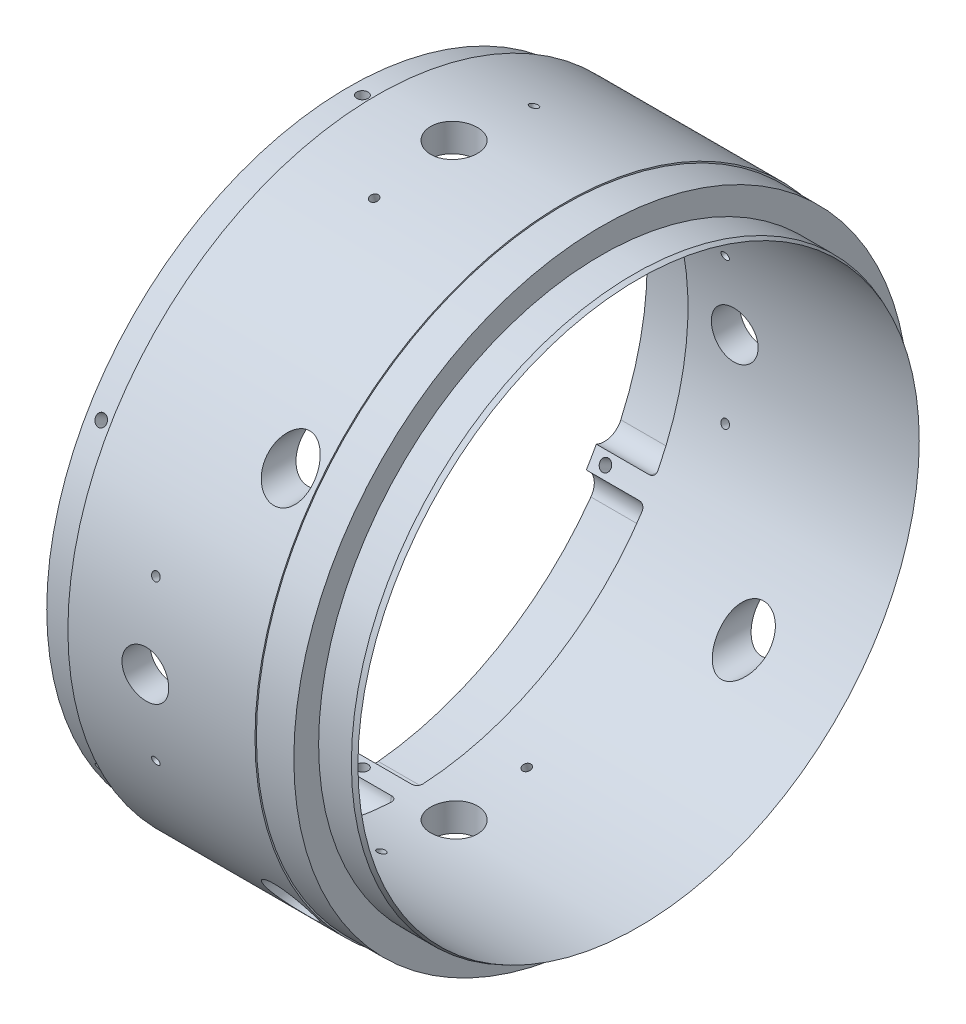
SolidWorks part; units mm, degrees
note: '?' marks a value the reader was unsure of.
material "6061-T6 (SS)"
ref_plane "Front" through (0, 0, 0) normal (0, 0, 1) x (1, 0, 0)
ref_plane "Top" through (0, 0, 0) normal (0, 1, 0) x (1, 0, 0)
ref_plane "Right" through (0, 0, 0) normal (1, 0, 0) x (0, 0, -1)
sketch "Sketch1" plane through (0, 0, 0) normal (0, 0, 1) x (1, 0, 0)
  line L0 (-10.16, 0.508) -> (-1.27, 0.508)
  line L1 (-71.12, 7.62) -> (-20.32, 7.62)
  line L2 (-10.16, 7.239) -> (-10.16, 0.508)
  line L3 (0, 0) -> (-78.7908, 0)
  line L4 (-1.27, 0.508) -> (0, 0)
  line L5 (-78.7908, 5.6896) -> (-78.7908, 0)
  line L6 (-71.12, 7.62) -> (-71.12, 5.6896)
  line L7 (-71.12, 5.6896) -> (-78.7908, 5.6896)
  line L8 (-44.3099, -76.2) -> (29.4033, -76.2) construction
  line L9 (-20.32, 7.62) -> (-20.32, 7.239)
  line L10 (-20.32, 7.239) -> (-10.16, 7.239)
  dimension "D1" = 7.6708
  dimension "D2" = 0.508
  dimension "D3" = 50.8
  dimension "D4" = 10.16
  dimension "D5" = 76.2
  dimension "D6" = 5.6896
  dimension "D7" = 6.731
  dimension "D8" = 0.381
  dimension "D9" = 10.16
  dimension "D10" = 1.27
revolve "Revolve2" add sketch "Sketch1" angle 360 about L8
ref_point "Point1"
ref_plane "Plane1" through (0, -76.2, 0) normal (0, 1, 0) x (1, 0, 0)
ref_plane "Plane2" through (0, -158.0896, 0) normal (0, -1, 0) x (-1, 0, 0)
hole_wizard "#31 (0.12) Diameter Hole1" positions "3DSketch1" profile "Sketch11" hole size "#31" standard "ANSI Inch"
sketch3d "3DSketch1"
  point P0 (-74.9808, -158.0896, 0)
  dimension "D1" = 3.81
sketch "Sketch11" plane through (-74.9808, -158.0896, 0) normal (1, 0, 0) x (0, 0, -1)
  line L0 (0, 0) -> (0, 185.9821)
  line L1 (0, 185.9821) -> (1.524, 185.9821)
  line L2 (1.524, 185.9821) -> (1.524, 0)
  line L5 (1.524, 0) -> (0, 0)
  line L11 (0, -6.35) -> (0, 107.95) construction
  dimension "Thru Hole Dia." = 3.048
  dimension "Thru Hole Depth" = 185.9821
pattern_circular "CirPattern4" count 6 over 360 about axis through (-44.3099, -76.2, 0) along (-1, 0, 0) of "#31 (0.12) Diameter Hole1"
sketch "Sketch8" plane through (-78.7908, 0, 0) normal (-1, 0, 0) x (0, 0, 1)
  line L0 (-7.6343, -152.0166) -> (0, -76.2) construction
  line L1 (0, -76.2) -> (0, -152.4) construction
  line L2 (-61.8419, -120.7198) -> (0, -76.2) construction
  line L3 (0, -76.2) -> (-65.9911, -114.3) construction
  circle A0 centre (0, -76.2) radius 76.2 construction
  arc A1 (-65.841, -123.5988) -> (-8.128, -156.9194) centre (0, -76.2) ccw
  circle A2 centre (0, -76.2) radius 81.8896 construction
  circle A3 centre (0, -76.2) radius 76.2
  arc A4 (-64.5901, -116.6297) -> (-2.7181, -152.3515) centre (0, -76.2) ccw
  circle A5 centre (0, -76.2) radius 81.8896
  circle A6 centre (-61.8419, -120.7198) radius 4.9276
  circle A7 centre (-7.6343, -152.0166) radius 4.9276
  arc A8 (-1.524, -158.0754) -> (1.524, -158.0754) centre (0, -76.2) ccw construction
  arc A9 (-1.524, -152.3848) -> (1.524, -152.3848) centre (0, -76.2) ccw construction
  arc A10 (-1.524, -158.0754) -> (1.524, -158.0754) centre (0, -76.2) ccw
  arc A11 (-1.524, -152.3848) -> (1.524, -152.3848) centre (0, -76.2) ccw
  arc A12 (-64.5901, -116.6297) -> (-2.7181, -152.3515) centre (0, -76.2) ccw
  arc A13 (-66.7399, -112.9726) -> (-65.2159, -115.6122) centre (0, -76.2) ccw construction
  arc A14 (-66.7399, -112.9726) -> (-65.2159, -115.6122) centre (0, -76.2) ccw
  arc A15 (-71.6682, -115.8179) -> (-70.1442, -118.4575) centre (0, -76.2) ccw construction
  arc A16 (-71.6682, -115.8179) -> (-70.1442, -118.4575) centre (0, -76.2) ccw
  point P3 (0, -152.4)
  point P14 (-8.128, -156.9194)
  point P16 (-65.841, -123.5988)
  point P20 (-65.9911, -114.3)
  dimension "D2" = 5.75
  dimension "D3" = 0.762
  dimension "D4" = 5.75
  dimension "D1" = 0
extrude "Cut-Extrude1" cut sketch "Sketch8" against normal blind 16.002
fillet "Fillet1" radius 1.5875 3 edges at (-62.7888, -155.7816, -4.4553) (-62.7888, -146.4586, -40.5638) (-62.7888, -119.8492, -66.692)
pattern_circular "CirPattern3" count 6 over 360 about axis through (0, -76.2, 0) along (1, 0, 0) of "Cut-Extrude1", "Fillet1"
sketch3d "3DSketch2"
  circle A0 centre (-24.9799, -157.9493, -0.0042) radius 2.0193
  point P2 (-24.9799, -155.93, -0.0042)
  dimension "D1" = 4.0386
sketch "Sketch12" plane through (0, 0, 0) normal (0, 0, 1) x (1, 0, 0)
  line L0 (-71.12, -76.2) -> (-20.32, -76.2) construction
  line L1 (-62.7888, -41.8886) -> (-62.7888, -110.5114) construction
  line L3 (-71.12, 7.62) -> (-71.12, -160.02) construction
  line L4 (-20.32, -159.639) -> (-20.32, 7.239) construction
  line L5 (-50.0888, -76.2) -> (-50.0888, 7.62) construction
  line L7 (-20.32, 7.62) -> (-71.12, 7.62) construction
  circle A0 centre (-50.0888, -76.2) radius 6.35
  dimension "D1" = 12.7
  dimension "D2" = 12.7
extrude "Cut-Extrude2" cut sketch "Sketch12" against normal through all
mirror "Mirror1" about plane through (0, 0, 0) normal (0, 0, 1) of "Cut-Extrude2"
sketch "Sketch13" plane through (0, 0, 0) normal (0, 1, 0) x (1, 0, 0)
  line L0 (-71.12, 0) -> (-20.32, 0) construction
  line L1 (-71.12, 81.8896) -> (-71.12, -81.8896) construction
  line L2 (-20.32, -83.82) -> (-20.32, 83.82) construction
  line L3 (-62.7888, 63.7335) -> (-62.7888, 4.3045) construction
  circle A0 centre (-50.0888, 0) radius 6.35
  dimension "D1" = 12.7
  dimension "D2" = 12.7
extrude "Cut-Extrude3" cut sketch "Sketch13" against normal through all and the other way through all
ref_axis "Axis1" through (-50.0888, -76.2, -83.82) along (0, 0, 1)?
ref_axis "Axis2" through (-50.0888, -165.5859, 0) along (0, 1, 0)?
hole_wizard "#4-40 Tapped Hole1" positions "3DSketch3" profile "Sketch14" tap size "#4-40" standard "ANSI Inch"
sketch3d "3DSketch3"
  line L0 (-50.0888, -76.2, -83.82) -> (-50.0888, -76.2, 89.7205) construction
  line L3 (-50.0888, -56.478, -73.6035) -> (-50.0888, -44.2107, -70.3165) construction
  line L5 (-50.0888, -95.922, -73.6035) -> (-50.0888, -108.1893, -70.3165) construction
  line L7 (-50.0888, -149.8035, -19.722) -> (-50.0888, -146.5165, -31.9893) construction
  line L9 (-50.0888, -149.8035, 19.722) -> (-50.0888, -146.5165, 31.9893) construction
  line L10 (-50.0888, -95.922, 73.6035) -> (-50.0888, -108.1893, 70.3165) construction
  line L12 (-50.0888, -56.478, 73.6035) -> (-50.0888, -44.2107, 70.3165) construction
  line L13 (-50.0888, -165.5859, 0) -> (-50.0888, 7.62, 0) construction
  line L14 (-50.0888, -2.5965, 19.722) -> (-50.0888, -5.8835, 31.9893) construction
  line L16 (-50.0888, -2.5965, -19.722) -> (-50.0888, -5.8835, -31.9893) construction
  circle A5 centre (-50.0888, -76.2, 0) radius 76.2
  point P0 (-50.0888, -56.478, -73.6035)
  point P2 (-50.0888, -95.922, -73.6035)
  point P4 (-50.0888, -2.5965, -19.722)
  point P6 (-50.0888, -2.5965, 19.722)
  point P8 (-50.0888, -95.922, 73.6035)
  point P10 (-50.0888, -56.478, 73.6035)
  point P19 (-50.0888, -149.8035, 19.722)
  point P21 (-50.0888, -149.8035, -19.722)
  point P50 (26.1112, -76.2, 0)
  dimension "D1" = 12.7
  dimension "D3" = 15
  dimension "D4" = 15
  dimension "D5" = 15
  dimension "D6" = 15
sketch "Sketch14" plane through (-50.0888, -56.478, -73.6035) normal (1, 0, 0) x (0, -0.9659, -0.2588)
  line L0 (0, 0) -> (0, 9.5438)
  line L1 (0, 9.5438) -> (1.1303, 8.8646)
  line L2 (1.1303, 8.8646) -> (1.1303, 0)
  line L5 (1.1303, 0) -> (0, 0)
  line L10 (0, 9.5438) -> (-1.1303, 8.8646) construction
  line L11 (0, -6.35) -> (0, 107.95) construction
  dimension "Tap Drill Dia." = 2.2606
  dimension "Tap Drill Depth" = 8.8646
  dimension "Drill Angle" = 118
cosmetic thread "Hole Thread1" parameters "D1"=5.6896, "D2"=2.8448
cosmetic thread "Hole Thread2" parameters "D1"=5.6896, "D2"=2.8448
cosmetic thread "Hole Thread3" parameters "D1"=5.6896, "D2"=2.8448
cosmetic thread "Hole Thread4" parameters "D1"=5.6896, "D2"=2.8448
cosmetic thread "Hole Thread5" parameters "D1"=5.6896, "D2"=2.8448
cosmetic thread "Hole Thread6" parameters "D1"=5.6896, "D2"=2.8448
cosmetic thread "Hole Thread7" parameters "D1"=5.6896, "D2"=2.8448
cosmetic thread "Hole Thread8" parameters "D1"=5.6896, "D2"=2.8448
ref_axis "Axis3" through (0, -76.2, 0) along (-1, 0, 0)?
sketch "Sketch15" plane through (0, 0, 0) normal (0, 0, 1) x (1, 0, 0)
  line L0 (-27.94, 7.62) -> (-27.94, -160.02) construction
  line L1 (-20.32, 7.62) -> (-43.7388, 7.62) construction
  line L2 (-43.7388, -160.02) -> (-20.32, -160.02) construction
  line L3 (-20.32, -160.02) -> (-20.32, 7.62) construction
  line L4 (-78.7908, -76.2) -> (0, -76.2) construction
  line L5 (-78.7908, 5.6896) -> (-78.7908, -158.0896) construction
  line L6 (0, 0) -> (0, -152.4) construction
  circle A0 centre (-27.94, -25.4) radius 6.35
  circle A1 centre (-27.94, -127) radius 6.35
  dimension "D2" = 12.7
  dimension "D1" = 7.62
  dimension "D3" = 50.8
extrude "Cut-Extrude4" cut sketch "Sketch15" against normal through all and the other way through all
